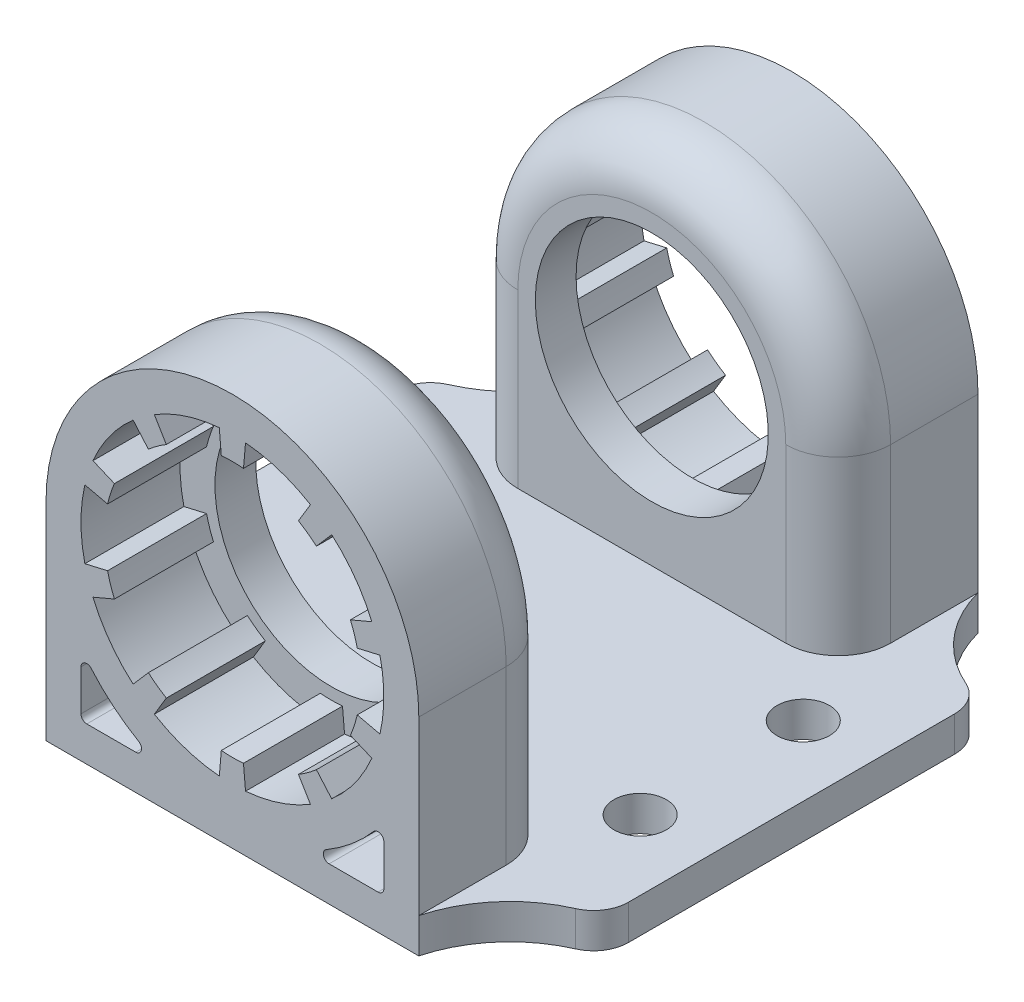
SolidWorks part; units mm, degrees
ref_plane "Alzado" through (0, 0, 0) normal (0, 0, 1) x (1, 0, 0)
ref_plane "Planta" through (0, 0, 0) normal (0, 1, 0) x (1, 0, 0)
ref_plane "Vista lateral" through (0, 0, 0) normal (1, 0, 0) x (0, 0, -1)
sketch "Croquis2" plane through (0, 0, 0) normal (0, 0, 1) x (1, 0, 0)
  line L1 (0, 0) -> (-32, 0)
  line L2 (0, 0) -> (0, 17.76)
  line L4 (-32, 0) -> (-32, 17.76)
  arc A0 (0, 17.76) -> (-32, 17.76) centre (-16, 17.76) ccw
  dimension "D1" = 32
  dimension "D2" = 17.76
extrude "Saliente-Extruir1" add sketch "Croquis2" along normal mid plane 12
sketch "Croquis3" plane through (0, 0, 6) normal (0, 0, 1) x (1, 0, 0)
  circle A0 centre (-16, 17.76) radius 4
  dimension "D1" = 8
extrude "Cortar-Extruir1" cut sketch "Croquis3" against normal through all
ref_plane "Plano1" through (-16, 0, 0) normal (-1, 0, 0) x (0, 0, 1)
sketch "Croquis4" plane through (0, 0, 6) normal (0, 0, 1) x (1, 0, 0)
  circle A0 centre (-16, 17.76) radius 13
  dimension "D1" = 26
extrude "Cortar-Extruir2" cut sketch "Croquis4" against normal blind 8.5
sketch "Croquis5" plane through (0, 0, -2.5) normal (0, 0, 1) x (1, 0, 0)
  circle A0 centre (-16, 17.76) radius 10
  dimension "D1" = 20
extrude "Cortar-Extruir3" cut sketch "Croquis5" against normal blind 8.5
sketch "Croquis6" plane through (0, 0, -6) normal (0, 0, -1) x (-1, 0, 0)
  line L0 (32, 17.76) -> (32, 0) construction
  line L1 (0, 0) -> (32, 0)
  line L2 (0, 0) -> (0, 3)
  line L3 (0, 3) -> (32, 3)
  line L4 (32, 0) -> (32, 3)
  dimension "D1" = 3
extrude "Saliente-Extruir2" add sketch "Croquis6" along normal blind 24
ref_plane "Plano2" through (0, 0, -18) normal (0, 0, -1) x (-1, 0, 0)
mirror "Simetría1" about plane through (0, 0, -18) normal (0, 0, -1) of "Cortar-Extruir3", "Cortar-Extruir2", "Saliente-Extruir1"
sketch "Croquis7" plane through (0, 0, 0) normal (0, 1, 0) x (1, 0, 0)
  line L0 (0, 42) -> (0, 30) construction
  line L1 (0, 35) -> (5, 35)
  line L2 (0, 35) -> (0, 1)
  line L3 (0, 1) -> (5, 1)
  line L4 (8, 32) -> (8, 4)
  line L5 (0, 42) -> (-32, 42) construction
  line L6 (-32, -6) -> (0, -6) construction
  line L7 (-16, 42) -> (-16, 38.616) construction
  line L8 (-32, 1) -> (-37, 1)
  line L9 (-40, 32) -> (-40, 4)
  line L10 (-32, 35) -> (-37, 35)
  line L11 (-32, 35) -> (-32, 1)
  arc A0 (5, 1) -> (8, 4) centre (5, 4) ccw
  arc A1 (5, 35) -> (8, 32) centre (5, 32) cw
  arc A2 (-37, 1) -> (-40, 4) centre (-37, 4) cw
  arc A3 (-37, 35) -> (-40, 32) centre (-37, 32) ccw
  dimension "D4" = 3
  dimension "D1" = 7
  dimension "D2" = 7
  dimension "D3" = 8
extrude "Saliente-Extruir3" add sketch "Croquis7" along normal blind 3
fillet "Redondeo1" radius 11 4 edges at (0, 1.5, -35) (0, 1.5, -1) (-32, 1.5, -1) (-32, 1.5, -35)
sketch "Croquis8" plane through (0, 3, 0) normal (0, 1, 0) x (1, 0, 0)
  line L0 (8, 4) -> (8, 32) construction
  line L2 (17.6, 18) -> (-17.6, 18) construction
  circle A0 centre (2, 25) radius 2.25
  circle A1 centre (2, 11) radius 2.25
  dimension "D1" = 4.5
  dimension "D2" = 6
  dimension "D3" = 7
extrude "Cortar-Extruir4" cut sketch "Croquis8" against normal through all
mirror "Simetría2" about plane through (-16, 0, 0) normal (-1, 0, 0) of "Cortar-Extruir4"
sketch "Croquis11" plane through (0, 0, 6) normal (0, 0, 1) x (1, 0, 0)
  line L0 (-17.125, 30.7112) -> (-16.9519, 28.7187)
  line L1 (-14.875, 30.7112) -> (-15.0481, 28.7187)
  line L2 (-16, 30.76) -> (-16, 28.76) construction
  circle A0 centre (-16, 17.76) radius 16 construction
  arc A2 (-15.0481, 28.7187) -> (-16.9519, 28.7187) centre (-16, 17.76) ccw
  circle A3 centre (-16, 17.76) radius 13 construction
  arc A4 (-14.875, 30.7112) -> (-17.125, 30.7112) centre (-16, 17.76) ccw
  dimension "D1" = 32
  dimension "D2" = 2.25
  dimension "D3" = 22
extrude "Saliente-Extruir4" add sketch "Croquis11" against normal up to surface (8.5 mm away) up to face at (-6, 17.76, -2.5)
pattern_circular "MatrizC1" count 10 over 360 about axis through (-16, 17.76, 6) along (0, 0, 1) of "Saliente-Extruir4"
mirror "Simetría3" about plane through (0, 0, -18) normal (0, 0, -1) of "MatrizC1", "Saliente-Extruir4"
fillet "Redondeo2" radius 4.5 6 edges at (0, 10.38, -6) (-32, 10.38, -6) (-16, 33.76, -6) (0, 10.38, -30) (-32, 10.38, -30) (-16, 33.76, -30)
sketch "Croquis12" plane through (0, 0, 6) normal (0, 0, 1) x (1, 0, 0)
  line L0 (-3, 3.5) -> (-3, 6.9897)
  line L1 (0, 3) -> (0, 17.76) construction
  line L2 (-3.5, 3) -> (-7.6993, 3)
  line L3 (-32, 0) -> (0, 0) construction
  arc A0 (-7.9508, 3.9321) -> (-3.8788, 7.316) centre (-16, 17.76) ccw
  arc A1 (-3, 3.5) -> (-3.5, 3) centre (-3.5, 3.5) cw
  arc A2 (-3, 6.9897) -> (-3.8788, 7.316) centre (-3.5, 6.9897) ccw
  arc A3 (-7.6993, 3) -> (-7.9508, 3.9321) centre (-7.6993, 3.5) cw
  dimension "D3" = 32
  dimension "D4" = 0.5
  dimension "D1" = 3
  dimension "D2" = 3
extrude "Cortar-Extruir5" cut sketch "Croquis12" against normal blind 9
mirror "Simetría4" about plane through (-16, 0, 0) normal (-1, 0, 0) of "Cortar-Extruir5"
mirror "Simetría5" about plane through (0, 0, -18) normal (0, 0, -1) of "Simetría4", "Cortar-Extruir5"
